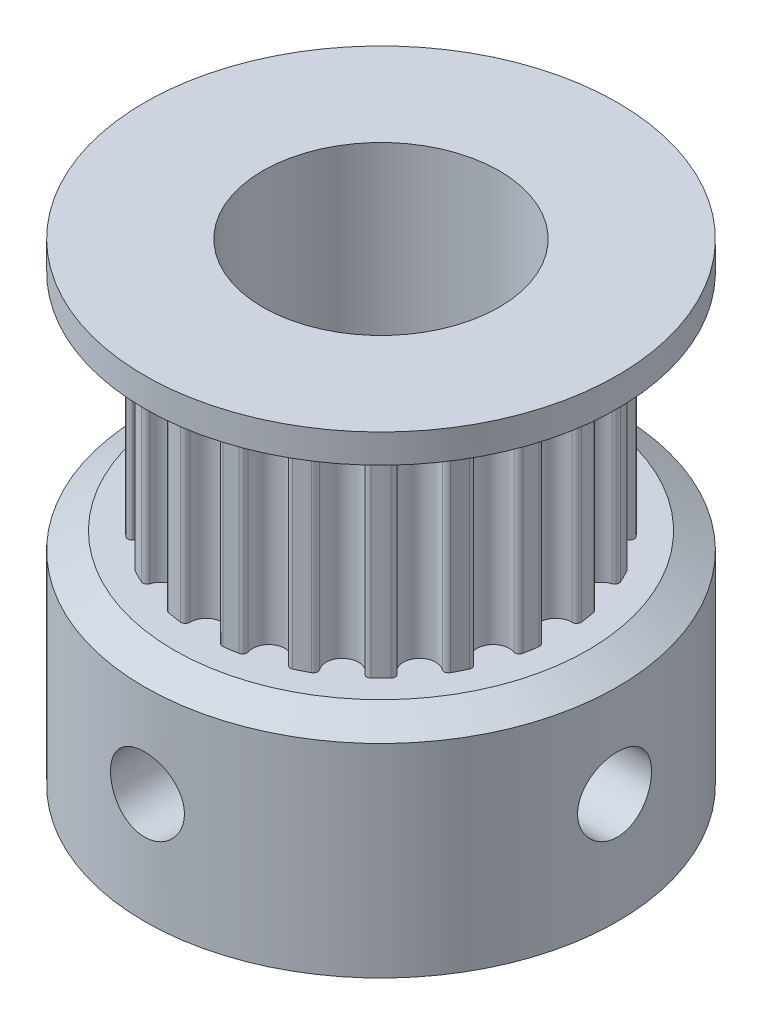
SolidWorks part; units mm, degrees
note: '?' marks a value the reader was unsure of.
material "1060 Сплав"
ref_plane "Спереди" through (0, 0, 0) normal (0, 0, 1) x (1, 0, 0)
ref_plane "Сверху" through (0, 0, 0) normal (0, 1, 0) x (1, 0, 0)
ref_plane "Справа" through (0, 0, 0) normal (1, 0, 0) x (0, 0, -1)
other "Configuration Table"
sketch "Эскиз1" plane through (0, 0, 0) normal (0, 1, 0) x (1, 0, 0)
  circle A0 centre (0, 0) radius 8
  circle A1 centre (0, 0) radius 4
  dimension "D1" = 16
  dimension "D2" = 8
extrude "Бобышка-Вытянуть1" add sketch "Эскиз1" along normal blind 7.45
sketch "Эскиз2" plane through (0, 7.45, 0) normal (0, 1, 0) x (1, 0, 0)
  arc A0 (-2.5575, 5.549) -> (-2.986, 5.3307) centre (0, 0) ccw
  circle A1 centre (0, 0) radius 4 construction
  circle A2 centre (0, 0) radius 4
  arc A3 (-0.55, 5.9169) -> (0.55, 5.9169) centre (0, 5.91) ccw
  arc A4 (1.3054, 5.7972) -> (2.3515, 5.4573) centre (1.8263, 5.6207) ccw
  arc A5 (3.0329, 5.1101) -> (3.9228, 4.4636) centre (3.4738, 4.7813) ccw
  arc A6 (4.4636, 3.9228) -> (5.1101, 3.0329) centre (4.7813, 3.4738) ccw
  arc A7 (5.4573, 2.3515) -> (5.7972, 1.3054) centre (5.6207, 1.8263) ccw
  arc A8 (5.9169, 0.55) -> (5.9169, -0.55) centre (5.91, 0) ccw
  arc A9 (5.7972, -1.3054) -> (5.4573, -2.3515) centre (5.6207, -1.8263) ccw
  arc A10 (5.1101, -3.0329) -> (4.4636, -3.9228) centre (4.7813, -3.4738) ccw
  arc A11 (3.9228, -4.4636) -> (3.0329, -5.1101) centre (3.4738, -4.7813) ccw
  arc A12 (2.3515, -5.4573) -> (1.3054, -5.7972) centre (1.8263, -5.6207) ccw
  arc A13 (0.55, -5.9169) -> (-0.55, -5.9169) centre (0, -5.91) ccw
  arc A14 (-1.3054, -5.7972) -> (-2.3515, -5.4573) centre (-1.8263, -5.6207) ccw
  arc A15 (-3.0329, -5.1101) -> (-3.9228, -4.4636) centre (-3.4738, -4.7813) ccw
  arc A16 (-4.4636, -3.9228) -> (-5.1101, -3.0329) centre (-4.7813, -3.4738) ccw
  arc A17 (-5.4573, -2.3515) -> (-5.7972, -1.3054) centre (-5.6207, -1.8263) ccw
  arc A18 (-5.9169, -0.55) -> (-5.9169, 0.55) centre (-5.91, 0) ccw
  arc A19 (-5.7972, 1.3054) -> (-5.4573, 2.3515) centre (-5.6207, 1.8263) ccw
  arc A20 (-5.1101, 3.0329) -> (-4.4636, 3.9228) centre (-4.7813, 3.4738) ccw
  arc A21 (-3.9228, 4.4636) -> (-3.0329, 5.1101) centre (-3.4738, 4.7813) ccw
  arc A22 (-2.3515, 5.4573) -> (-1.3054, 5.7972) centre (-1.8263, 5.6207) ccw
  arc A23 (-4.147, 4.4871) -> (-4.4871, 4.147) centre (0, 0) ccw
  arc A24 (-0.7176, 6.0677) -> (-1.1926, 5.9925) centre (0, 0) ccw
  arc A25 (1.1926, 5.9925) -> (0.7176, 6.0677) centre (0, 0) ccw
  arc A26 (2.986, 5.3307) -> (2.5575, 5.549) centre (0, 0) ccw
  arc A27 (4.4871, 4.147) -> (4.147, 4.4871) centre (0, 0) ccw
  arc A28 (5.549, 2.5575) -> (5.3307, 2.986) centre (0, 0) ccw
  arc A29 (6.0677, 0.7176) -> (5.9925, 1.1926) centre (0, 0) ccw
  arc A30 (-5.3307, 2.986) -> (-5.549, 2.5575) centre (0, 0) ccw
  arc A31 (-5.9925, 1.1926) -> (-6.0677, 0.7176) centre (0, 0) ccw
  arc A32 (-6.0677, -0.7176) -> (-5.9925, -1.1926) centre (0, 0) ccw
  arc A33 (-5.549, -2.5575) -> (-5.3307, -2.986) centre (0, 0) ccw
  arc A34 (-4.4871, -4.147) -> (-4.147, -4.4871) centre (0, 0) ccw
  arc A35 (-2.986, -5.3307) -> (-2.5575, -5.549) centre (0, 0) ccw
  arc A36 (5.9925, -1.1926) -> (6.0677, -0.7176) centre (0, 0) ccw
  arc A37 (5.3307, -2.986) -> (5.549, -2.5575) centre (0, 0) ccw
  arc A38 (4.147, -4.4871) -> (4.4871, -4.147) centre (0, 0) ccw
  arc A39 (2.5575, -5.549) -> (2.986, -5.3307) centre (0, 0) ccw
  arc A40 (0.7176, -6.0677) -> (1.1926, -5.9925) centre (0, 0) ccw
  arc A41 (-1.1926, -5.9925) -> (-0.7176, -6.0677) centre (0, 0) ccw
  arc A42 (5.9169, 0.55) -> (6.0677, 0.7176) centre (5.9188, 0.6999) ccw
  arc A43 (5.7972, 1.3054) -> (5.9925, 1.1926) centre (5.8454, 1.1633) cw
  arc A44 (5.4573, 2.3515) -> (5.549, 2.5575) centre (5.4128, 2.4947) ccw
  arc A45 (5.1101, 3.0329) -> (5.3307, 2.986) centre (5.1998, 2.9127) cw
  arc A46 (5.1101, -3.0329) -> (5.3307, -2.986) centre (5.1998, -2.9127) ccw
  arc A47 (5.4573, -2.3515) -> (5.549, -2.5575) centre (5.4128, -2.4947) cw
  arc A48 (5.7972, -1.3054) -> (5.9925, -1.1926) centre (5.8454, -1.1633) ccw
  arc A49 (5.9169, -0.55) -> (6.0677, -0.7176) centre (5.9188, -0.6999) cw
  arc A50 (3.9228, -4.4636) -> (4.147, -4.4871) centre (4.0452, -4.377) ccw
  arc A51 (4.4636, -3.9228) -> (4.4871, -4.147) centre (4.377, -4.0452) cw
  arc A52 (3.0329, -5.1101) -> (2.986, -5.3307) centre (2.9127, -5.1998) cw
  arc A53 (1.3054, -5.7972) -> (1.1926, -5.9925) centre (1.1633, -5.8454) cw
  arc A54 (0.55, -5.9169) -> (0.7176, -6.0677) centre (0.6999, -5.9188) ccw
  arc A55 (-0.55, -5.9169) -> (-0.7176, -6.0677) centre (-0.6999, -5.9188) cw
  arc A56 (-1.3054, -5.7972) -> (-1.1926, -5.9925) centre (-1.1633, -5.8454) ccw
  arc A57 (-2.3515, -5.4573) -> (-2.5575, -5.549) centre (-2.4947, -5.4128) cw
  arc A58 (-3.0329, -5.1101) -> (-2.986, -5.3307) centre (-2.9127, -5.1998) ccw
  arc A59 (-3.9228, -4.4636) -> (-4.147, -4.4871) centre (-4.0452, -4.377) cw
  arc A60 (-4.4636, -3.9228) -> (-4.4871, -4.147) centre (-4.377, -4.0452) ccw
  arc A61 (-5.9169, -0.55) -> (-6.0677, -0.7176) centre (-5.9188, -0.6999) ccw
  arc A62 (-5.7972, -1.3054) -> (-5.9925, -1.1926) centre (-5.8454, -1.1633) cw
  arc A63 (-5.4573, -2.3515) -> (-5.549, -2.5575) centre (-5.4128, -2.4947) ccw
  arc A64 (-5.1101, -3.0329) -> (-5.3307, -2.986) centre (-5.1998, -2.9127) cw
  arc A65 (-5.1101, 3.0329) -> (-5.3307, 2.986) centre (-5.1998, 2.9127) ccw
  arc A66 (-5.4573, 2.3515) -> (-5.549, 2.5575) centre (-5.4128, 2.4947) cw
  arc A67 (-5.7972, 1.3054) -> (-5.9925, 1.1926) centre (-5.8454, 1.1633) ccw
  arc A68 (-5.9169, 0.55) -> (-6.0677, 0.7176) centre (-5.9188, 0.6999) cw
  arc A69 (-4.4636, 3.9228) -> (-4.4871, 4.147) centre (-4.377, 4.0452) cw
  arc A70 (-3.9228, 4.4636) -> (-4.147, 4.4871) centre (-4.0452, 4.377) ccw
  arc A71 (-3.0329, 5.1101) -> (-2.986, 5.3307) centre (-2.9127, 5.1998) cw
  arc A72 (-2.3515, 5.4573) -> (-2.5575, 5.549) centre (-2.4947, 5.4128) ccw
  arc A73 (-1.3054, 5.7972) -> (-1.1926, 5.9925) centre (-1.1633, 5.8454) cw
  arc A74 (-0.55, 5.9169) -> (-0.7176, 6.0677) centre (-0.6999, 5.9188) ccw
  arc A75 (4.4636, 3.9228) -> (4.4871, 4.147) centre (4.377, 4.0452) ccw
  arc A76 (3.9228, 4.4636) -> (4.147, 4.4871) centre (4.0452, 4.377) cw
  arc A77 (0.55, 5.9169) -> (0.7176, 6.0677) centre (0.6999, 5.9188) cw
  arc A78 (1.3054, 5.7972) -> (1.1926, 5.9925) centre (1.1633, 5.8454) ccw
  arc A79 (3.0329, 5.1101) -> (2.986, 5.3307) centre (2.9127, 5.1998) ccw
  arc A80 (2.3515, 5.4573) -> (2.5575, 5.549) centre (2.4947, 5.4128) cw
  arc A81 (2.3515, -5.4573) -> (2.5575, -5.549) centre (2.4947, -5.4128) ccw
  point P69 (0, 0)
  point P135 (-0.5205, 6.0878)
  point P142 (0.5205, 6.0878)
  dimension "D1" = 12.22
  dimension "D2" = 1.1
  dimension "D3" = 0.75
  dimension "D5" = 0.15
  dimension "D6" = 0.15
  dimension "D4" = 20
extrude "Бобышка-Вытянуть2" add sketch "Эскиз2" along normal blind 7
sketch "Эскиз3" plane through (0, 14.45, 0) normal (0, 1, 0) x (1, 0, 0)
  circle A0 centre (0, 0) radius 4 construction
  circle A1 centre (0, 0) radius 4
  circle A2 centre (0, 0) radius 8 construction
  circle A3 centre (0, 0) radius 8
extrude "Бобышка-Вытянуть3" add sketch "Эскиз3" along normal blind 1.55
sketch "Эскиз4" plane through (0, 0, 0) normal (0, 0, 1) x (1, 0, 0)
  line L0 (-8, 3.725) -> (8, 3.725) construction
  line L1 (-8, 7.45) -> (-8, 0) construction
  line L2 (8, 0) -> (8, 7.45) construction
  circle A0 centre (0, 3.725) radius 1.25
  dimension "D1" = 2.5
extrude "Вырез-Вытянуть1" cut sketch "Эскиз4" along normal up to surface (7.9017 mm away)
sketch "Эскиз5" plane through (0, 0, 0) normal (1, 0, 0) x (0, 0, -1)
  line L0 (8, 3.725) -> (-7.9017, 3.725) construction
  line L1 (8, 0) -> (8, 7.45) construction
  circle A0 centre (0, 3.725) radius 1.25
  spline S1 degree 2 poles (-8, 4.975) (-7.8047, 3.725) (-8, 2.475) knots 0 0 0 1 1 1 weights 0.00675 0.008 0.00925 construction
  dimension "D1" = 2.5
extrude "Вырез-Вытянуть2" cut sketch "Эскиз5" along normal up to surface (7.9017 mm away)
sketch "Минимальный радиус ремня" plane through (0, 7.45, 0) normal (0, 1, 0) x (1, 0, 0)
  circle A0 centre (0, 0) radius 5.36
  arc A2 (-2.986, -5.3307) -> (-2.5575, -5.549) centre (0, 0) ccw construction
  dimension "D1" = 0.75
  dimension "D2" = 10.72
chamfer "Фаска1" distance 1 angle 30 2 edges at (0, 14.45, 8) (0, 7.45, 8)
ref_axis "Ось1" through (0, 16, 0) along (0, -1, 0)?
